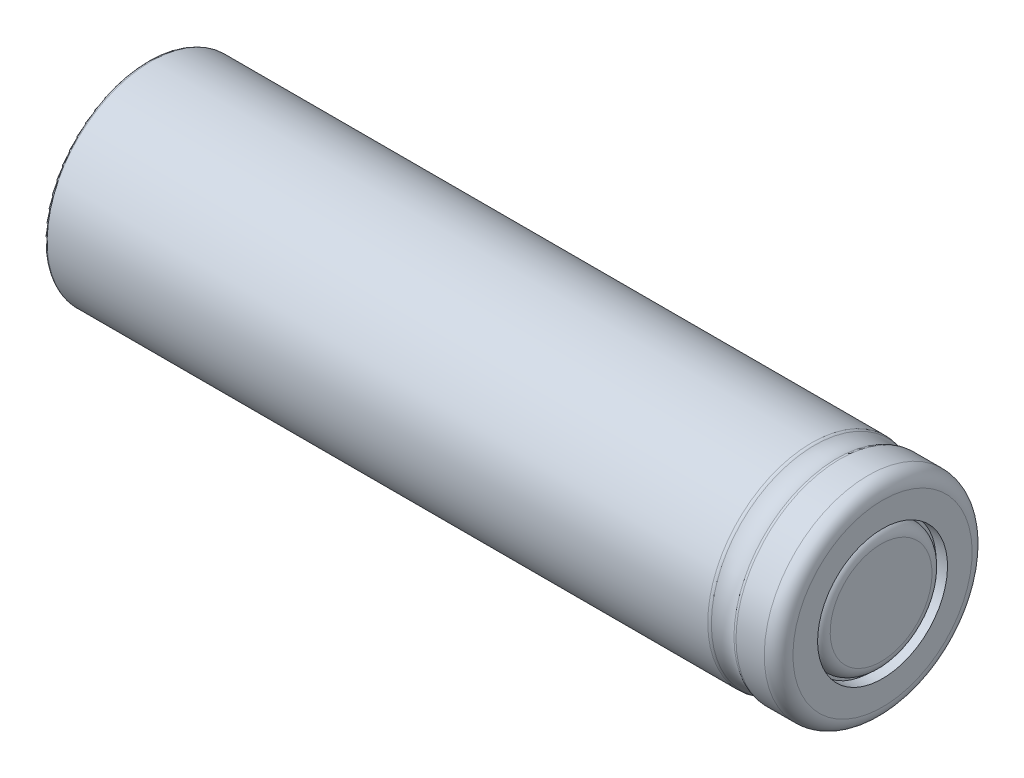
SolidWorks part; units mm, degrees
ref_plane "Front" through (0, 0, 0) normal (0, 0, 1) x (1, 0, 0)
ref_plane "Top" through (0, 0, 0) normal (0, 1, 0) x (1, 0, 0)
ref_plane "Right" through (0, 0, 0) normal (1, 0, 0) x (0, 0, -1)
sketch "Sketch1" plane through (0, 0, 0) normal (0, 0, 1) x (1, 0, 0)
  line L0 (0, 0) -> (0, 8.946)
  line L1 (0.254, 9.2) -> (63.73, 9.2)
  line L2 (65, 7.93) -> (65, 0)
  line L3 (65, 0) -> (0, 0)
  arc A0 (0.254, 9.2) -> (0, 8.946) centre (0.254, 8.946) ccw
  arc A1 (65, 7.93) -> (63.73, 9.2) centre (63.73, 7.93) ccw
  dimension "D1" = 0.254
  dimension "D4" = 1.27
  dimension "D2" = 65
  dimension "D3" = 9.2
revolve "base" add sketch "Sketch1" angle 360 about L3
sketch "Sketch2" plane through (0, 0, 0) normal (0, 0, 1) x (1, 0, 0)
  line L0 (63.73, 9.2) -> (61.23, 9.2)
  line L2 (0, 0) -> (64.5761, 0) construction
  line L3 (61.23, 9.2) -> (58.73, 9.2)
  line L4 (58.73, 9.2) -> (0, 9.2)
  arc A0 (60.98, 9.133) -> (58.98, 9.133) centre (59.98, 10.8651) cw
  arc A1 (58.98, 9.133) -> (58.73, 9.2) centre (58.73, 8.7) ccw
  arc A2 (61.23, 9.2) -> (60.98, 9.133) centre (61.23, 8.7) ccw
  point P0 (63.73, 9.2)
  dimension "D1" = 0.5
  dimension "D3" = 2
  dimension "D2" = 2.5
  dimension "D4" = 2.5
revolve "+ notch" cut sketch "Sketch2" angle 360 about L2 region at (59.98, 9.0658, 0)
sketch "Sketch3" plane through (65, 0, 0) normal (1, 0, 0) x (0, 0, -1)
  circle A0 centre (0, 0) radius 5.75
  dimension "D1" = 11.5
extrude "Extrude1" cut sketch "Sketch3" against normal blind 1.016
sketch "Sketch4" plane through (63.984, 0, 0) normal (1, 0, 0) x (0, 0, -1)
  circle A0 centre (0, 0) radius 5.5
  dimension "D1" = 11
extrude "Extrude3" add sketch "Sketch4" along normal offset from surface (0.889 mm away) 0.127 up to face at (65, 5.75, 0)
sketch "Sketch5" plane through (0, 0, 0) normal (-1, 0, 0) x (0, 0, 1)
  circle A0 centre (0, 0) radius 7.5
  dimension "D1" = 15
extrude "Extrude4" cut sketch "Sketch5" against normal blind 0.0254
fillet "Fillet1" radius 1 1 edges at (64.873, 5.5, 0)
